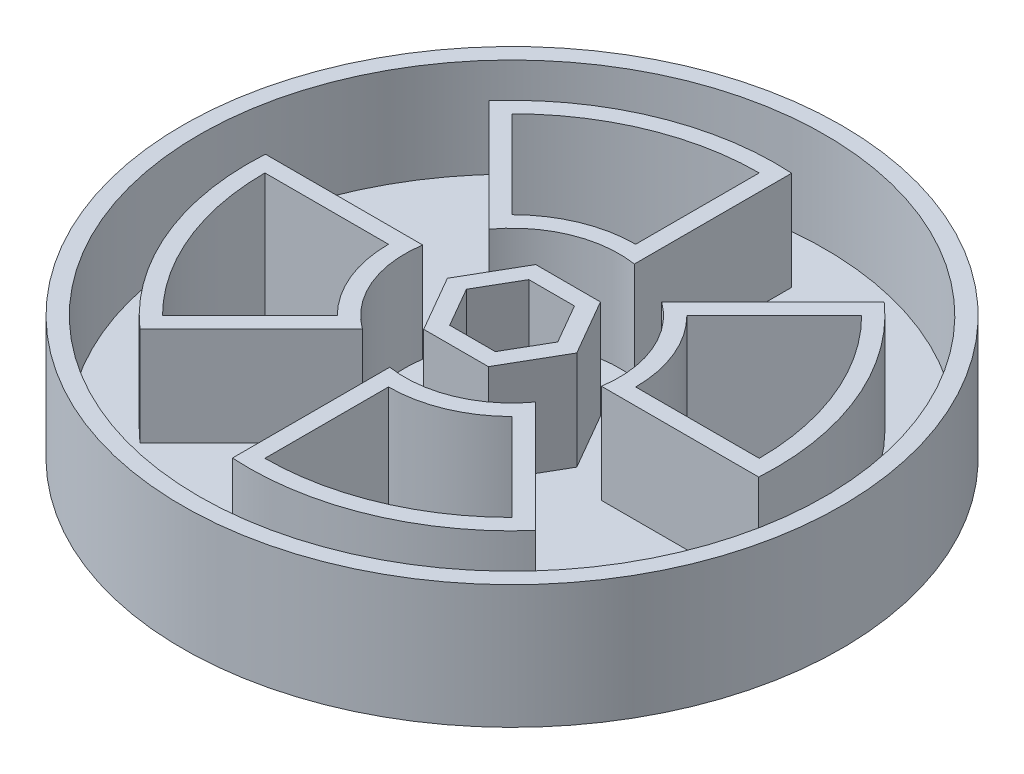
SolidWorks part; units mm, degrees
ref_plane "Front Plane" through (0, 0, 0) normal (0, 0, 1) x (1, 0, 0)
ref_plane "Top Plane" through (0, 0, 0) normal (0, 1, 0) x (1, 0, 0)
ref_plane "Right Plane" through (0, 0, 0) normal (1, 0, 0) x (0, 0, -1)
sketch "Sketch1" plane through (0, 0, 0) normal (0, 1, 0) x (1, 0, 0)
  circle A0 centre (0, 0) radius 50.8
  dimension "D1" = 101.6
extrude "Boss-Extrude1" add sketch "Sketch1" along normal blind 19.05
sketch "Sketch4" plane through (0, 19.05, 0) normal (0, 1, 0) x (1, 0, 0)
  line L0 (-3.5195, 6.096) -> (3.5195, 6.096)
  line L1 (3.5195, 6.096) -> (7.0391, 0)
  line L2 (7.0391, 0) -> (3.5195, -6.096)
  line L3 (3.5195, -6.096) -> (-3.5195, -6.096)
  line L4 (-3.5195, -6.096) -> (-7.0391, 0)
  line L5 (-7.0391, 0) -> (-3.5195, 6.096)
  point P7 (0, 6.096)
  dimension "D1" = 120
  dimension "D2" = 12.192
extrude "Cut-Extrude2" cut sketch "Sketch4" against normal blind 15.24 contours L5 L0 L1 L2 L3 L4
sketch "Sketch5" plane through (0, 3.81, 0) normal (0, 1, 0) x (1, 0, 0)
  circle A0 centre (0, 0) radius 4.064
  dimension "D1" = 8.128
extrude "Cut-Extrude3" cut sketch "Sketch5" against normal through all contours A0
sketch "Sketch6" plane through (0, 19.05, 0) normal (0, 1, 0) x (1, 0, 0)
  line L0 (0, 0) -> (0, 38.1)
  line L1 (0, 0) -> (26.9408, 26.9408)
  line L2 (0, 0) -> (38.1, 0)
  line L3 (0, 0) -> (26.9408, -26.9408)
  line L4 (0, 0) -> (0, -38.1)
  line L5 (0, 0) -> (-26.9408, -26.9408)
  line L6 (0, 0) -> (-38.1, 0)
  line L7 (0, 0) -> (-26.9408, 26.9408)
  circle A0 centre (0, 0) radius 38.1
  circle A1 centre (0, 0) radius 19.05
  point P15 (0, 0)
  dimension "D1" = 38.1
  dimension "D2" = 76.2
  dimension "D3" = 45
  dimension "D4" = 4
extrude "Cut-Extrude4" cut sketch "Sketch6" against normal through all contours A1 L0 A0 L7 | A1 L2 A0 L1 | A1 L4 A0 L3 | A1 L6 A0 L5 region at (-11.051, 19.05, -26.6794) region at (26.6794, 19.05, -11.051) region at (11.051, 19.05, 26.6794) region at (-26.6794, 19.05, 11.051)
sketch "Sketch7" plane through (0, 19.05, 0) normal (0, 1, 0) x (1, 0, 0)
  line L27 (16.3134, -2.54) -> (40.5605, -2.54)
  line L28 (26.8846, 30.4767) -> (9.7393, 13.3314)
  line L29 (2.54, 16.3134) -> (2.54, 40.5605)
  line L30 (-30.4767, 26.8846) -> (-13.3314, 9.7393)
  line L31 (2.54, 16.3134) -> (2.54, 40.5605)
  line L32 (-30.4767, 26.8846) -> (-13.3314, 9.7393)
  line L33 (-2.54, -16.3134) -> (-2.54, -40.5605)
  line L34 (30.4767, -26.8846) -> (13.3314, -9.7393)
  line L35 (-16.3134, 2.54) -> (-40.5605, 2.54)
  line L36 (-26.8846, -30.4767) -> (-9.7393, -13.3314)
  line L64 (9.972, 0) -> (4.986, 8.636)
  line L65 (4.986, -8.636) -> (9.972, 0)
  line L66 (-4.986, -8.636) -> (4.986, -8.636)
  line L67 (-9.972, 0) -> (-4.986, -8.636)
  line L68 (-4.986, 8.636) -> (-9.972, 0)
  line L69 (4.986, 8.636) -> (-4.986, 8.636)
  line L70 (9.972, 0) -> (4.986, 8.636)
  line L71 (4.986, -8.636) -> (9.972, 0)
  line L72 (-4.986, -8.636) -> (4.986, -8.636)
  line L73 (-9.972, 0) -> (-4.986, -8.636)
  line L74 (-4.986, 8.636) -> (-9.972, 0)
  line L75 (4.986, 8.636) -> (-4.986, 8.636)
  arc A28 (40.5605, -2.54) -> (26.8846, 30.4767) centre (0, 0) ccw
  arc A29 (16.3134, -2.54) -> (9.7393, 13.3314) centre (0, 0) ccw
  arc A30 (2.54, 16.3134) -> (-13.3314, 9.7393) centre (0, 0) ccw
  arc A31 (2.54, 40.5605) -> (-30.4767, 26.8846) centre (0, 0) ccw
  arc A32 (2.54, 16.3134) -> (-13.3314, 9.7393) centre (0, 0) ccw
  arc A33 (2.54, 40.5605) -> (-30.4767, 26.8846) centre (0, 0) ccw
  arc A34 (-2.54, -40.5605) -> (30.4767, -26.8846) centre (0, 0) ccw
  arc A35 (-2.54, -16.3134) -> (13.3314, -9.7393) centre (0, 0) ccw
  arc A36 (-40.5605, 2.54) -> (-26.8846, -30.4767) centre (0, 0) ccw
  arc A37 (-16.3134, 2.54) -> (-9.7393, -13.3314) centre (0, 0) ccw
  circle A40 centre (0, 0) radius 48.26
  circle A41 centre (0, 0) radius 50.8 construction
  point P15 (0, 0)
  dimension "D4" = 2.54
  dimension "D1" = 2.54
  dimension "D3" = 2.54
  dimension "D2" = 4
extrude "Cut-Extrude5" cut sketch "Sketch7" against normal up to surface (15.24 mm away) contours A40 L35 A37 L36 A36 L27 A29 L28 A28 L75 L70 L71 L72 L73 L74 A33 L31 A32 L32 L33 A35 L34 A34 region at (-46.895, 19.05, 0) up to face at (0, 3.81, 4.064)
